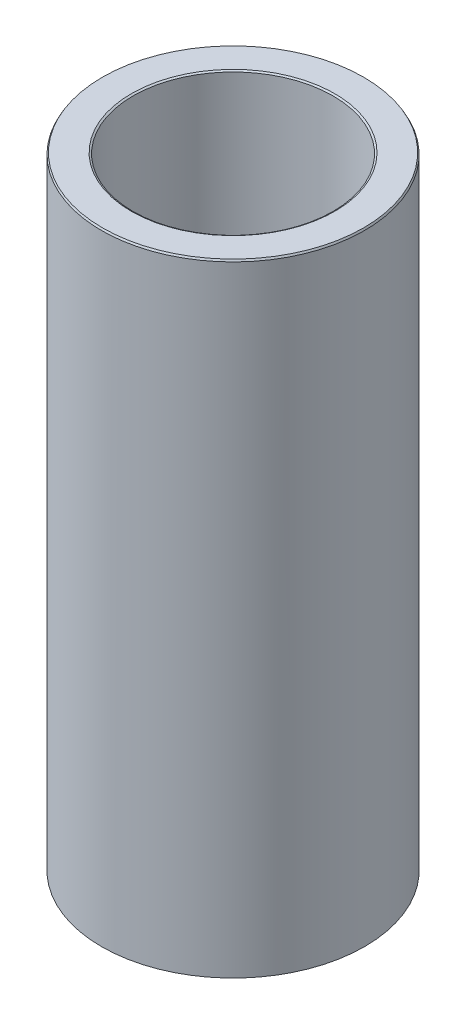
SolidWorks part; units mm, degrees
ref_plane "Front Plane" through (0, 0, 0) normal (0, 0, 1) x (1, 0, 0)
ref_plane "Top Plane" through (0, 0, 0) normal (0, 1, 0) x (1, 0, 0)
ref_plane "Right Plane" through (0, 0, 0) normal (1, 0, 0) x (0, 0, -1)
sketch "Sketch1" plane through (0, 0, 0) normal (0, 1, 0) x (1, 0, 0)
  circle A0 centre (0, 0) radius 25
  dimension "SLEEVE_OD" = 50
extrude "Boss-Extrude1" add sketch "Sketch1" along normal blind 118.365
sketch "Sketch2" plane through (0, 0, 0) normal (0, 1, 0) x (1, 0, 0)
  circle A0 centre (0, 0) radius 19.0121
  dimension "BORE_D" = 38.0242
extrude "Cut-Extrude1" cut sketch "Sketch2" along normal through all
chamfer "Chamfer1" distance 0.3334 angle 30 4 edges at (0, 118.365, 19.0121) (0, 0, 19.0121) (0, 0, 25) (0, 118.365, 25) first distance on face at (0, 118.365, 19.0121) first distance on face at (0, 0, 19.0121) first distance on face at (0, 118.365, 25)
